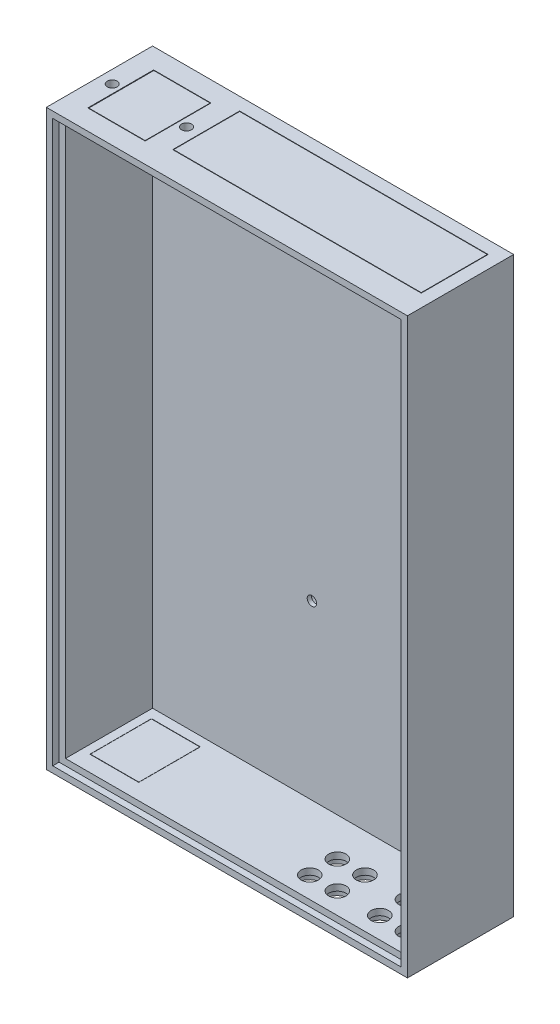
SolidWorks part; units mm, degrees
ref_plane "Front Plane" through (0, 0, 0) normal (0, 0, 1) x (1, 0, 0)
ref_plane "Top Plane" through (0, 0, 0) normal (0, 1, 0) x (1, 0, 0)
ref_plane "Right Plane" through (0, 0, 0) normal (1, 0, 0) x (0, 0, -1)
sketch "Sketch1" plane through (0, 0, 0) normal (0, 0, 1) x (1, 0, 0)
  line L1 (-42.4109, 60.2306) -> (127.5891, 60.2306)
  line L2 (-42.4109, 60.2306) -> (-42.4109, -209.7694)
  line L3 (-42.4109, -209.7694) -> (127.5891, -209.7694)
  line L4 (127.5891, 60.2306) -> (127.5891, -209.7694)
  dimension "D1" = 170
  dimension "D2" = 270
extrude "Boss-Extrude1" add sketch "Sketch1" along normal blind 50
sketch "Sketch2" plane through (0, 0, 50) normal (0, 0, 1) x (1, 0, 0)
  line L0 (-42.4109, 60.2306) -> (-42.4109, -209.7694) construction
  line L1 (-36.4109, 54.2306) -> (121.5891, 54.2306)
  line L2 (-36.4109, 54.2306) -> (-36.4109, -203.7694)
  line L3 (-36.4109, -203.7694) -> (121.5891, -203.7694)
  line L4 (121.5891, 54.2306) -> (121.5891, -203.7694)
  line L5 (127.5891, -209.7694) -> (127.5891, 60.2306) construction
  line L6 (-42.4109, -209.7694) -> (127.5891, -209.7694) construction
  line L7 (127.5891, 60.2306) -> (-42.4109, 60.2306) construction
  dimension "D1" = 6
  dimension "D2" = 6
  dimension "D3" = 6
  dimension "D4" = 6
extrude "Cut-Extrude1" cut sketch "Sketch2" against normal blind 44
sketch "Sketch3" plane through (0, -209.7694, 0) normal (0, -1, 0) x (1, 0, 0)
  line L0 (-42.4109, 50) -> (-42.4109, 0) construction
  line L1 (-32.4109, 39.5) -> (-9.4109, 39.5)
  line L2 (-32.4109, 39.5) -> (-32.4109, 10.5)
  line L3 (-32.4109, 10.5) -> (-9.4109, 10.5)
  line L4 (-9.4109, 39.5) -> (-9.4109, 10.5)
  line L5 (-42.4109, 0) -> (127.5891, 0) construction
  dimension "D1" = 23
  dimension "D2" = 29
  dimension "D3" = 10
  dimension "D4" = 10.5
extrude "Cut-Extrude2" cut sketch "Sketch3" against normal blind 6
sketch "Sketch4" plane through (0, -209.7694, 0) normal (0, -1, 0) x (1, 0, 0)
  line L0 (-9.4109, 39.5) -> (-32.4109, 39.5) construction
  line L1 (-34.9109, 42.5) -> (-6.9109, 42.5)
  line L2 (-34.9109, 42.5) -> (-34.9109, 7.5)
  line L3 (-34.9109, 7.5) -> (-6.9109, 7.5)
  line L4 (-6.9109, 42.5) -> (-6.9109, 7.5)
  line L5 (-32.4109, 10.5) -> (-9.4109, 10.5) construction
  line L6 (-32.4109, 39.5) -> (-32.4109, 10.5) construction
  line L7 (-9.4109, 10.5) -> (-9.4109, 39.5) construction
  dimension "D1" = 3
  dimension "D2" = 3
  dimension "D3" = 2.5
  dimension "D4" = 2.5
extrude "Cut-Extrude3" cut sketch "Sketch4" against normal blind 4.5
chamfer "Chamfer1" distance 5 angle 45 1 edges at (-20.9109, -209.7694, 42.5)
chamfer "Chamfer2" distance 5 angle 45 1 edges at (-20.9109, -209.7694, 7.5)
sketch "Sketch5" plane through (0, -205.2694, 0) normal (0, -1, 0) x (1, 0, 0)
  line L0 (-32.4109, 10.5) -> (-32.4109, 39.5) construction
  line L1 (-32.3109, 39.35) -> (-9.5109, 39.35)
  line L2 (-32.3109, 39.35) -> (-32.3109, 10.65)
  line L3 (-32.3109, 10.65) -> (-9.5109, 10.65)
  line L4 (-9.5109, 39.35) -> (-9.5109, 10.65)
  line L5 (-9.4109, 39.5) -> (-9.4109, 10.5) construction
  line L6 (-9.4109, 10.5) -> (-32.4109, 10.5) construction
  line L7 (-32.4109, 39.5) -> (-9.4109, 39.5) construction
  dimension "D1" = 0.1
  dimension "D2" = 0.1
  dimension "D3" = 0.15
  dimension "D4" = 0.15
extrude "Boss-Extrude2" add sketch "Sketch5" against normal blind 1.5 separate body
sketch "Sketch6" plane through (0, -81.1347, -81.1347) normal (0, -0.7071, -0.7071) x (1, 0, 0)
  text T0 "I" font "Century Gothic" height in points 18
extrude "Cut-Extrude4" cut sketch "Sketch6" against normal blind 0.25
sketch "Sketch7" plane through (0, -106.1347, 106.1347) normal (0, -0.7071, 0.7071) x (1, 0, 0)
  text T0 "0" font "Century Gothic" height in points 15
extrude "Cut-Extrude5" cut sketch "Sketch7" against normal blind 0.25
sketch "Sketch8" plane through (0, -209.7694, 0) normal (0, -1, 0) x (1, 0, 0)
  text T0 "24V PS" font "Century Gothic" height in points 20
extrude "Cut-Extrude6" cut sketch "Sketch8" against normal blind 0.25
sketch "Sketch9" plane through (0, 54.2306, 0) normal (0, -1, 0) x (1, 0, 0)
  line L1 (121.5891, 6) -> (4.5891, 6)
  line L2 (121.5891, 6) -> (121.5891, 37.5)
  line L3 (121.5891, 37.5) -> (4.5891, 37.5)
  line L4 (4.5891, 6) -> (4.5891, 37.5)
  dimension "D1" = 31.5
  dimension "D2" = 117
extrude "Cut-Extrude7" cut sketch "Sketch9" against normal blind 6
sketch "Sketch10" plane through (0, 60.2306, 0) normal (0, 1, 0) x (1, 0, 0)
  line L0 (127.5891, -50) -> (-42.4109, -50) construction
  line L1 (-5.4109, -40.5) -> (-32.4109, -40.5)
  line L2 (-5.4109, -40.5) -> (-5.4109, -9.5)
  line L3 (-5.4109, -9.5) -> (-32.4109, -9.5)
  line L4 (-32.4109, -40.5) -> (-32.4109, -9.5)
  line L8 (-42.4109, -50) -> (-42.4109, 0) construction
  dimension "D1" = 27
  dimension "D2" = 31
  dimension "D3" = 9.5
  dimension "D4" = 10
extrude "Cut-Extrude8" cut sketch "Sketch10" against normal blind 6
sketch "Sketch11" plane through (0, 60.2306, 0) normal (0, 1, 0) x (1, 0, 0)
  line L0 (-5.4109, -40.5) -> (-5.4109, -9.5) construction
  line L1 (-32.4109, -40.5) -> (-5.4109, -40.5) construction
  circle A0 centre (-1.4109, -25) radius 2.35
  dimension "D1" = 4.7
  dimension "D2" = 4
  dimension "D3" = 15.5
extrude "Cut-Extrude9" cut sketch "Sketch11" against normal blind 6
sketch "Sketch12" plane through (0, 60.2306, 0) normal (0, 1, 0) x (1, 0, 0)
  line L0 (-32.4109, -9.5) -> (-32.4109, -40.5) construction
  line L1 (-32.4109, -40.5) -> (-5.4109, -40.5) construction
  circle A0 centre (-36.4109, -25) radius 2.35
  dimension "D1" = 4.7
  dimension "D2" = 4
  dimension "D3" = 15.5
extrude "Cut-Extrude10" cut sketch "Sketch12" against normal blind 6
sketch "Sketch13" plane through (0, 60.2306, 0) normal (0, 1, 0) x (1, 0, 0)
  line L0 (4.5891, -37.5) -> (4.5891, -6) construction
  line L1 (4.7891, -6.2) -> (121.3891, -6.2)
  line L2 (4.7891, -6.2) -> (4.7891, -37.3)
  line L3 (4.7891, -37.3) -> (121.3891, -37.3)
  line L4 (121.3891, -6.2) -> (121.3891, -37.3)
  line L5 (-36.4109, -6) -> (121.5891, -6) construction
  line L6 (121.5891, -6) -> (121.5891, -50) construction
  line L7 (121.5891, -37.5) -> (4.5891, -37.5) construction
  dimension "D1" = 0.2
  dimension "D2" = 0.2
  dimension "D3" = 0.2
  dimension "D4" = 0.2
extrude "Boss-Extrude3" add sketch "Sketch13" against normal blind 6 separate body
sketch "Sketch14" plane through (0, 60.2306, 0) normal (0, 1, 0) x (1, 0, 0)
  line L0 (-32.3109, -39.35) -> (-32.3109, -10.65) construction
  line L1 (-5.6109, -40.3) -> (-32.1109, -40.3)
  line L2 (-5.6109, -40.3) -> (-5.6109, -9.7)
  line L3 (-5.6109, -9.7) -> (-32.1109, -9.7)
  line L4 (-32.1109, -40.3) -> (-32.1109, -9.7)
  line L5 (-5.4109, -40.5) -> (-5.4109, -9.5) construction
  line L6 (-5.4109, -9.5) -> (-32.4109, -9.5) construction
  line L7 (-32.4109, -40.5) -> (-5.4109, -40.5) construction
  dimension "D1" = 0.2
  dimension "D2" = 0.2
  dimension "D3" = 0.2
  dimension "D4" = 0.2
extrude "Boss-Extrude4" add sketch "Sketch14" against normal blind 6 separate body
sketch "Sketch15" plane through (0, -209.7694, 0) normal (0, -1, 0) x (1, 0, 0)
  line L0 (-42.4109, 50) -> (127.5891, 50) construction
  line L1 (127.5891, 50) -> (127.5891, 0) construction
  circle A0 centre (114.5891, 37) radius 4.1
  circle A1 centre (101.5891, 37) radius 4.1
  circle A2 centre (81.5891, 37) radius 4.1
  circle A3 centre (68.5891, 37) radius 4.1
  circle A4 centre (114.5891, 24) radius 4.1
  circle A5 centre (101.5891, 24) radius 4.1
  circle A6 centre (81.5891, 24) radius 4.1
  circle A7 centre (68.5891, 24) radius 4.1
  dimension "D1" = 8.2
  dimension "D2" = 8.2
  dimension "D3" = 8.2
  dimension "D4" = 8.2
  dimension "D5" = 8.2
  dimension "D6" = 8.2
  dimension "D7" = 8.2
  dimension "D8" = 8.2
  dimension "D9" = 13
  dimension "D10" = 13
  dimension "D11" = 13
  dimension "D12" = 13
  dimension "D13" = 13
  dimension "D14" = 13
  dimension "D15" = 13
  dimension "D16" = 13
  dimension "D17" = 13
  dimension "D18" = 13
  dimension "D19" = 13
  dimension "D20" = 20
  dimension "D21" = 13
extrude "Cut-Extrude11" cut sketch "Sketch15" against normal blind 6
sketch "Sketch16" plane through (0, -209.7694, 0) normal (0, -1, 0) x (1, 0, 0)
  circle A0 centre (114.5891, 37) radius 5.75
  circle A1 centre (114.5891, 24) radius 5.75
  circle A2 centre (101.5891, 37) radius 5.75
  circle A3 centre (101.5891, 24) radius 5.75
  circle A4 centre (81.5891, 37) radius 5.75
  circle A5 centre (68.5891, 37) radius 5.75
  circle A6 centre (81.5891, 24) radius 5.75
  circle A7 centre (68.5891, 24) radius 5.75
  dimension "D1" = 11.5
  dimension "D2" = 11.5
  dimension "D3" = 11.5
  dimension "D4" = 11.5
  dimension "D5" = 11.5
  dimension "D6" = 11.5
  dimension "D7" = 11.5
  dimension "D8" = 11.5
extrude "Cut-Extrude12" cut sketch "Sketch16" against normal blind 3
sketch "Sketch17" plane through (0, -209.7694, 0) normal (0, -1, 0) x (1, 0, 0)
  text T0 "+" font "Century Gothic" height in points 25
extrude "Cut-Extrude13" cut sketch "Sketch17" against normal blind 0.25
sketch "Sketch18" plane through (0, -209.7694, 0) normal (0, -1, 0) x (1, 0, 0)
  text T0 "-" font "Century Gothic" height in points 25
extrude "Cut-Extrude14" cut sketch "Sketch18" against normal blind 0.25
sketch "Sketch19" plane through (0, 0, 6) normal (0, 0, 1) x (1, 0, 0)
  line L0 (121.5891, -203.7694) -> (121.5891, 60.2306) construction
  line L1 (4.5891, 60.2306) -> (121.5891, 60.2306) construction
  circle A0 centre (88.5891, 27.4806) radius 2.2
  circle A1 centre (38.5891, 27.4806) radius 2.2
  circle A2 centre (88.5891, -122.5194) radius 2.2
  circle A3 centre (38.5891, -122.5194) radius 2.2
  dimension "D9" = 4.4
  dimension "D10" = 4.4
  dimension "D11" = 4.4
  dimension "D12" = 4.4
  dimension "D1" = 33
  dimension "D2" = 32.75
  dimension "D3" = 33
  dimension "D4" = 50
  dimension "D5" = 32.75
  dimension "D6" = 150
  dimension "D7" = 50
  dimension "D8" = 150
extrude "Cut-Extrude15" cut sketch "Sketch19" against normal blind 10
sketch "Sketch20" plane through (0, 0, 0) normal (0, 0, -1) x (-1, 0, 0)
  circle A0 centre (-88.5891, 27.4806) radius 3.75
  circle A1 centre (-38.5891, 27.4806) radius 3.75
  circle A2 centre (-38.5891, -122.5194) radius 3.75
  circle A3 centre (-88.5891, -122.5194) radius 3.75
  dimension "D1" = 7.5
  dimension "D2" = 7.5
  dimension "D3" = 7.5
  dimension "D4" = 7.5
extrude "Cut-Extrude16" cut sketch "Sketch20" against normal blind 4
sketch "Sketch21" plane through (0, 0, 50) normal (0, 0, 1) x (1, 0, 0)
  line L0 (121.5891, 54.2306) -> (-36.4109, 54.2306) construction
  line L1 (-39.4109, 57.2306) -> (124.5891, 57.2306)
  line L2 (-39.4109, 57.2306) -> (-39.4109, -206.7694)
  line L3 (-39.4109, -206.7694) -> (124.5891, -206.7694)
  line L4 (124.5891, 57.2306) -> (124.5891, -206.7694)
  line L5 (-36.4109, 54.2306) -> (-36.4109, -203.7694) construction
  line L6 (121.5891, -203.7694) -> (121.5891, 54.2306) construction
  line L7 (-36.4109, -203.7694) -> (121.5891, -203.7694) construction
  dimension "D1" = 3
  dimension "D2" = 3
  dimension "D3" = 3
  dimension "D4" = 3
extrude "Cut-Extrude17" cut sketch "Sketch21" against normal blind 3
